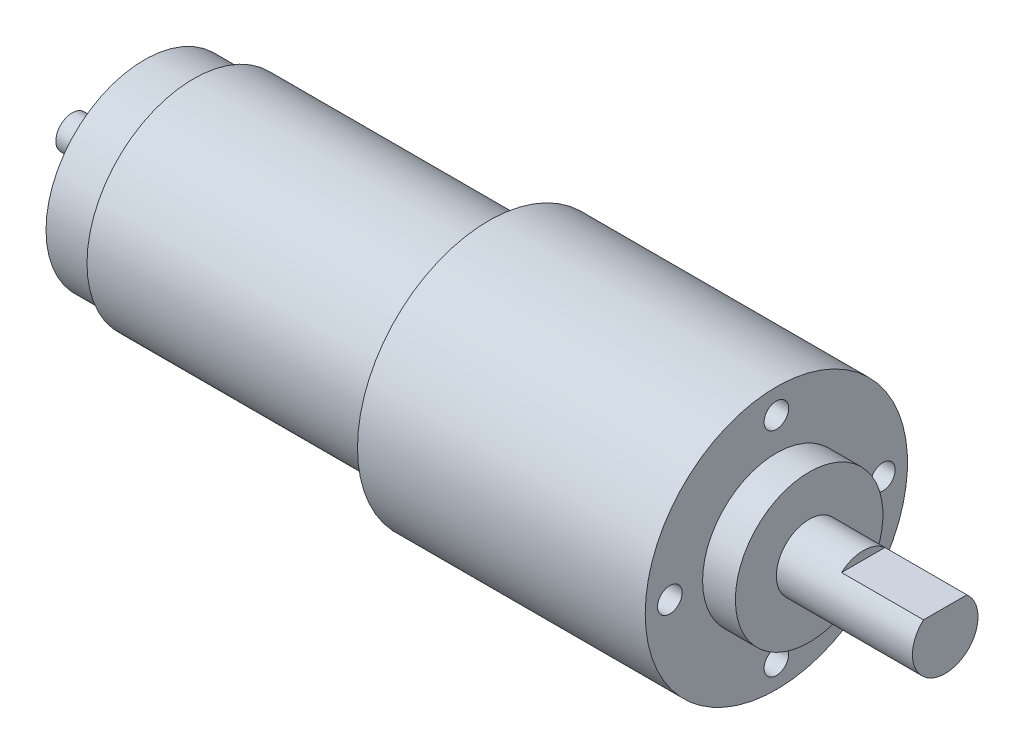
SolidWorks part; units mm, degrees
ref_plane "Plan de face" through (0, 0, 0) normal (0, 0, 1) x (1, 0, 0)
ref_plane "Plan de dessus" through (0, 0, 0) normal (0, 1, 0) x (1, 0, 0)
ref_plane "Plan de droite" through (0, 0, 0) normal (1, 0, 0) x (0, 0, -1)
ref_axis "Axe1" through (-5.325, 0, 0) along (1, 0, 0)
sketch "Esquisse1" plane through (0, 0, 0) normal (0, 0, 1) x (1, 0, 0)
  line L0 (0, 0) -> (106.5, 0)
  line L1 (106.5, 0) -> (106.5, 4)
  line L2 (106.5, 4) -> (89.9, 4)
  line L3 (89.9, 4) -> (89.9, 9)
  line L4 (89.9, 9) -> (85.9, 9)
  line L5 (85.9, 9) -> (85.9, 16)
  line L6 (85.9, 16) -> (50.8, 16)
  line L7 (50.8, 16) -> (50.8, 13)
  line L8 (50.8, 13) -> (14.8, 13)
  line L9 (14.8, 13) -> (14.8, 12)
  line L10 (14.8, 12) -> (8.8, 12)
  line L11 (8.8, 12) -> (8.8, 2)
  line L12 (8.8, 2) -> (0, 2)
  line L13 (0, 2) -> (0, 0)
  dimension "D1" = 35.1
  dimension "D2" = 4
  dimension "D3" = 20.6
  dimension "D4" = 13
  dimension "D5" = 16
  dimension "D6" = 9
  dimension "D7" = 12
  dimension "D8" = 2
  dimension "D9" = 42
  dimension "D10" = 6
  dimension "D11" = 8.8
  dimension "D12" = 4
  dimension "D13" = 106.5
revolve "MainRevolution" add sketch "Esquisse1" angle 360 about L0
sketch "Esquisse2" plane through (106.5, 0, 0) normal (1, 0, 0) x (0, 0, -1)
  line L1 (-2.6458, 3) -> (2.6458, 3)
  line L2 (-2.6458, 3) -> (-2.6458, 4)
  line L3 (-2.6458, 4) -> (2.6458, 4)
  line L4 (2.6458, 3) -> (2.6458, 4)
  circle A0 centre (0, 0) radius 4 construction
  circle A1 centre (0, 0) radius 4 construction
  dimension "D1" = 1
extrude "Enlèv. mat.-Extru.1" cut sketch "Esquisse2" against normal blind 10
sketch "Esquisse3" plane through (85.9, 0, 0) normal (1, 0, 0) x (0, 0, -1)
  line L0 (0, 17.6) -> (0, -17.6) construction
  circle A0 centre (0, 13) radius 1.5
  circle A1 centre (0, 0) radius 16 construction
  dimension "D1" = 3
  dimension "D2" = 13
extrude "FixHoles" cut sketch "Esquisse3" against normal blind 3
pattern_circular "RepeatFixHoles" count 4 every 90 about axis through (-5.325, 0, 0) along (1, 0, 0) of "FixHoles"
